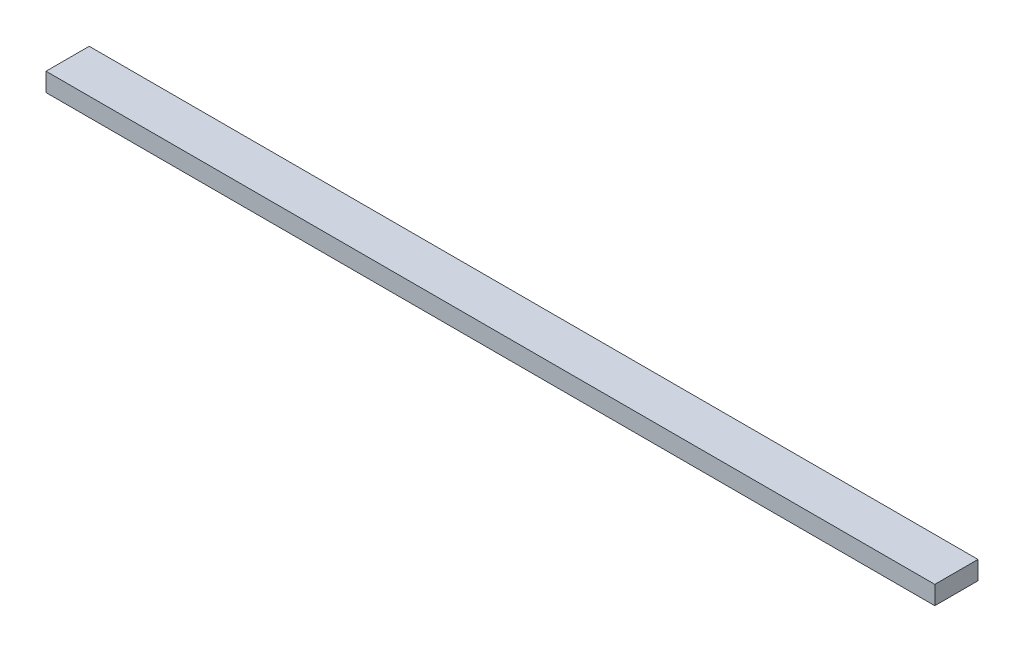
SolidWorks part; units mm, degrees
material "Pine"
ref_plane "Front Plane" through (0, 0, 0) normal (0, 0, 1) x (1, 0, 0)
ref_plane "Top Plane" through (0, 0, 0) normal (0, 1, 0) x (1, 0, 0)
ref_plane "Right Plane" through (0, 0, 0) normal (1, 0, 0) x (0, 0, -1)
sketch "Sketch1" plane through (0, 0, 0) normal (1, 0, 0) x (0, 0, -1)
  line L1 (44.45, -19.05) -> (-44.45, -19.05)
  line L2 (44.45, -19.05) -> (44.45, 19.05)
  line L3 (44.45, 19.05) -> (-44.45, 19.05)
  line L4 (-44.45, -19.05) -> (-44.45, 19.05)
  line L5 (44.45, -19.05) -> (-44.45, 19.05) construction
  line L6 (44.45, 19.05) -> (-44.45, -19.05) construction
  point P0 (0, 0)
  dimension "D1" = 88.9
  dimension "D2" = 38.1
extrude "Boss-Extrude1" add sketch "Sketch1" along normal up to surface (1828.8 mm away)
